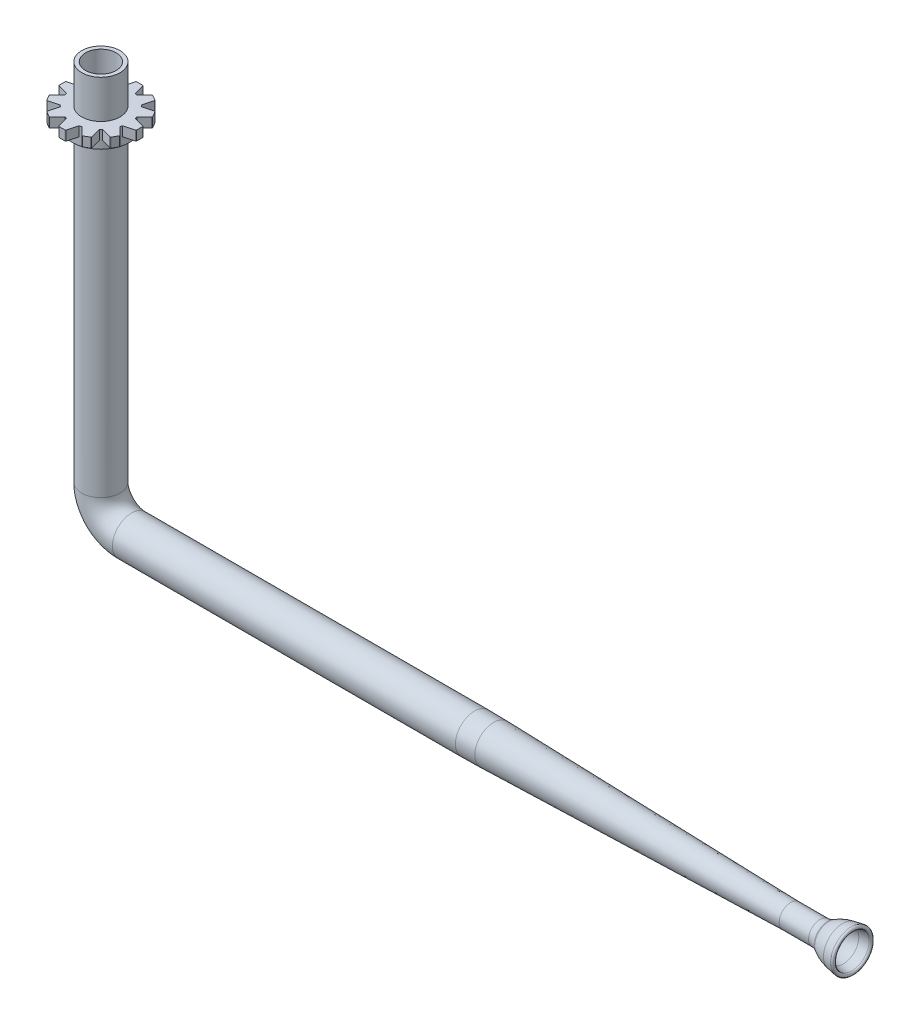
SolidWorks part; units mm, degrees
material "ABS"
ref_plane "Front Plane" through (0, 0, 0) normal (0, 0, 1) x (1, 0, 0)
ref_plane "Top Plane" through (0, 0, 0) normal (0, 1, 0) x (1, 0, 0)
ref_plane "Right Plane" through (0, 0, 0) normal (1, 0, 0) x (0, 0, -1)
sketch "Sketch1" plane through (0, 0, 0) normal (0, 1, 0) x (1, 0, 0)
  circle A0 centre (0, 0) radius 7.5
  dimension "D1" = 15
extrude "Boss-Extrude1" add sketch "Sketch1" along normal blind 2.5
sketch "Sketch2" plane through (0, 2.5, 0) normal (0, 1, 0) x (1, 0, 0)
  circle A0 centre (0, 0) radius 5
  circle A1 centre (0, 0) radius 4
  dimension "D1" = 10
  dimension "D2" = 8
extrude "Boss-Extrude2" add sketch "Sketch2" along normal blind 10 and the other way blind 83
sketch "Sketch3" plane through (0, 0, 0) normal (0, -1, 0) x (1, 0, 0)
  line L0 (0, 0) -> (0, 21.4338) construction
  line L1 (0, 10.1196) -> (0.9, 10.1196)
  line L2 (0.9, 10.1196) -> (1.6823, 7.2)
  line L3 (1.6823, 7.2) -> (-1.6823, 7.2)
  line L4 (-1.6823, 7.2) -> (-0.9, 10.1196)
  line L5 (-0.9, 10.1196) -> (0, 10.1196)
  line L6 (-0.9, 10.1196) -> (-6.2955, 10.1196) construction
  line L7 (0.9, 10.1196) -> (6.2539, 10.1196) construction
  dimension "D1" = 7.2
  dimension "D2" = 10.1196
  dimension "D3" = 0.9
  dimension "D4" = 0.9
  dimension "D5" = 75
  dimension "D6" = 75
extrude "Boss-Extrude3" add sketch "Sketch3" against normal blind 2.5 contours L2 L3 L4 L5 L1
fillet "Fillet1" radius 0.125 2 edges at (0.9, 1.25, 10.1196) (-0.9, 1.25, 10.1196)
pattern_circular "CirPattern1" count 12 over 360 about axis through (0, 2.5, 0) along (0, -1, 0) of "Boss-Extrude3", "Fillet1"
sketch "Sketch4" plane through (0, 2.5, 0) normal (0, 1, 0) x (1, 0, 0)
  circle A0 centre (0, 0) radius 4
  dimension "D1" = 8
extrude "Cut-Extrude1" cut sketch "Sketch4" against normal blind 2.5
sketch "Sketch5" plane through (0, -80.5, 0) normal (0, -1, 0) x (1, 0, 0)
  circle A0 centre (0, 0) radius 4
  circle A1 centre (0, 0) radius 5
  dimension "D1" = 10
  dimension "D2" = 8
sketch "Sketch6" plane through (0, 0, 0) normal (0, 0, 1) x (1, 0, 0)
  line L0 (0, -80.5) -> (0, -82.5)
  line L2 (-5, -80.5) -> (5, -80.5) construction
  line L3 (8, -90.5) -> (100, -90.5)
  arc A0 (0, -82.5) -> (8, -90.5) centre (8, -82.5) ccw
  point P8 (0, -90.5)
  dimension "D3" = 8
  dimension "D1" = 10
  dimension "D2" = 100
sweep "Sweep3" add profiles "Sketch5" path "Sketch6"
sketch "Sketch7" plane through (0, 0, 0) normal (0, 0, 1) x (1, 0, 0)
  line L0 (180, -90.5) -> (180, -88.5) construction
  line L1 (180, -88.5) -> (100, -86.5)
  line L2 (100, -85.5) -> (180, -87.5)
  line L3 (100, -85.5) -> (100, -86.5)
  line L4 (100, -90.5) -> (180, -90.5) construction
  line L5 (180, -87.5) -> (180, -88.5)
  dimension "D1" = 80
  dimension "D2" = 0
  dimension "D3" = 1
  dimension "D4" = 2
  dimension "D5" = 1
  dimension "D6" = 4
revolve "Revolve1" add sketch "Sketch7" angle 360 about L4
fillet "Fillet2" radius 200 1 edges at (100, -90.5, -5)
sketch "Sketch8" plane through (180, 0, 0) normal (1, 0, 0) x (0, 0, -1)
  circle A0 centre (0, -90.5) radius 2
  circle A1 centre (0, -90.5) radius 3
extrude "Boss-Extrude4" add sketch "Sketch8" along normal blind 5
sketch "Sketch9" plane through (0, 0, 0) normal (0, 0, 1) x (1, 0, 0)
  line L0 (185, -90.5) -> (200.3578, -90.5) construction
  line L1 (185, -93.5) -> (185, -87.5) construction
  line L2 (185, -88.5) -> (185, -90.5) construction
  line L3 (185, -88.5) -> (187.6603, -88.5)
  line L4 (190.1603, -87.8301) -> (190.473, -87.6496)
  line L5 (193.7365, -86.4618) -> (196, -86.0626)
  line L6 (185, -87.5) -> (187.6603, -87.5)
  line L7 (189.6603, -86.9641) -> (189.973, -86.7836)
  line L8 (193.5628, -85.477) -> (195.8264, -85.0778)
  line L9 (185, -87.5) -> (185, -88.5)
  arc A0 (190.473, -87.6496) -> (193.7365, -86.4618) centre (195.473, -96.3098) cw
  arc A1 (187.6603, -88.5) -> (190.1603, -87.8301) centre (187.6603, -83.5) ccw
  arc A2 (187.6603, -87.5) -> (189.6603, -86.9641) centre (187.6603, -83.5) ccw
  arc A3 (189.973, -86.7836) -> (193.5628, -85.477) centre (195.473, -96.3098) cw
  arc A4 (196, -86.0626) -> (195.8264, -85.0778) centre (195.9132, -85.5702) ccw
  point P10 (192, -86.7679)
  point P13 (189, -88.5)
  dimension "D7" = 10
  dimension "D8" = 5
  dimension "D10" = 0.5
  dimension "D1" = 2
  dimension "D2" = 4
  dimension "D3" = 3
  dimension "D4" = 30
  dimension "D5" = 200
  dimension "D6" = 4
  dimension "D9" = 1
revolve "Revolve2" add sketch "Sketch9" angle 360 about L0
sketch "Sketch10" plane through (0, 0, 0) normal (0, -1, 0) x (1, 0, 0)
  circle A0 centre (0, 0) radius 5
  circle A1 centre (0, 0) radius 7.5
extrude "Boss-Extrude5" add sketch "Sketch10" along normal blind 2
